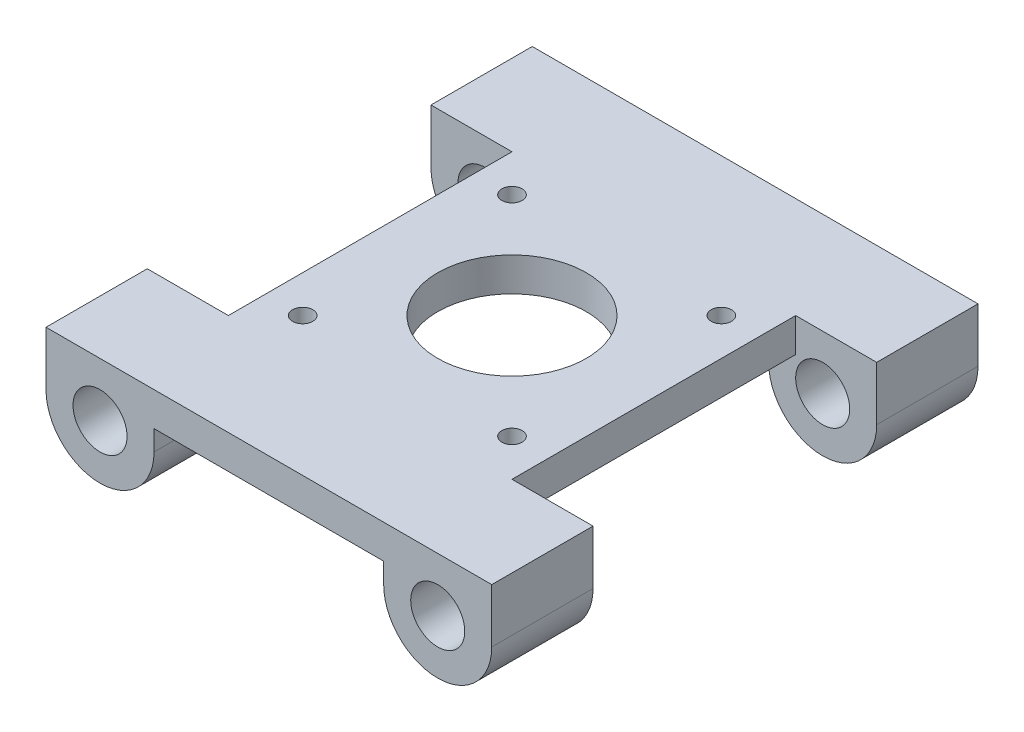
SolidWorks part; units mm, degrees
material "ABS"
ref_plane "Front Plane" through (0, 0, 0) normal (0, 0, 1) x (1, 0, 0)
ref_plane "Top Plane" through (0, 0, 0) normal (0, 1, 0) x (1, 0, 0)
ref_plane "Right Plane" through (0, 0, 0) normal (1, 0, 0) x (0, 0, -1)
sketch "Sketch1" plane through (0, 0, 0) normal (0, 0, 1) x (1, 0, 0)
  line L0 (0, 74.8863) -> (0, -94.3789) construction
  line L1 (33, 0) -> (-33, 0)
  line L2 (-33, 0) -> (-33, -8)
  line L3 (17, -5) -> (-17, -5)
  line L4 (-17, -5) -> (-17, -8)
  line L5 (17, -5) -> (17, -8)
  line L6 (33, 0) -> (33, -8)
  circle A0 centre (-25, -8) radius 4
  arc A1 (-33, -8) -> (-17, -8) centre (-25, -8) ccw
  arc A2 (33, -8) -> (17, -8) centre (25, -8) cw
  circle A3 centre (25, -8) radius 4
  point P16 (0, -5)
  point P17 (0, 0)
  dimension "D1" = 8
  dimension "D5" = 8
  dimension "D2" = 25
  dimension "D3" = 8
  dimension "D4" = 5
extrude "Boss-Extrude1" add sketch "Sketch1" against normal blind 15
sketch "Sketch2" plane through (0, 0, -15) normal (0, 0, -1) x (-1, 0, 0)
  line L0 (21, 0) -> (-21, 0)
  line L1 (-33, 0) -> (33, 0) construction
  line L2 (-21, 0) -> (-21, -5)
  line L3 (-21, -5) -> (21, -5)
  line L4 (17, -5) -> (-17, -5) construction
  line L5 (0, 7.9638) -> (0, -15.9981) construction
  line L6 (21, 0) -> (21, -5)
  point P12 (0, -5)
  point P13 (0, 0)
  dimension "D1" = 21
extrude "Boss-Extrude2" add sketch "Sketch2" along normal blind 42
extrude "Boss-Extrude3" add sketch "Sketch1<2>" against normal blind 15 from vertex starting at point (-21, 0, -57)
sketch "Sketch1<2>" plane through (0, 0, 0) normal (0, 0, 1) x (1, 0, 0) same geometry as "Sketch1"
sketch "Sketch3" plane through (0, 0, 0) normal (0, 1, 0) x (1, 0, 0)
  line L0 (0, -9.6218) -> (0, 80.5515) construction
  line L1 (-21, 36) -> (21, 36) construction
  line L2 (-21, 57) -> (-21, 15) construction
  line L3 (21, 57) -> (21, 15) construction
  circle A0 centre (-15.5, 51.5) radius 1.5
  circle A1 centre (0, 36) radius 11
  circle A2 centre (15.5, 51.5) radius 1.5
  circle A3 centre (15.5, 20.5) radius 1.5
  circle A4 centre (-15.5, 20.5) radius 1.5
  dimension "D1" = 3
  dimension "D4" = 22
  dimension "D2" = 15.5
  dimension "D3" = 15.5
  dimension "D5" = 2
  dimension "D6" = 2
extrude "Cut-Extrude1" cut sketch "Sketch3" against normal through all
equation "\"rod_diameter\"= 8"
equation "\"rod_hole_thickness\"= 4"
equation "\"rod_radius\"= \"rod_diameter\" / 2"
equation "\"platter_diameter\"= 320"
equation "\"platter_radius\"= \"platter_diameter\" / 2"
equation "\"extruder_mount_hole_spacing\"= 75"
equation "\"arm_rod_spacing\"= 40"
equation "\"top_frame_rod_spacing\"= \"arm_rod_spacing\" + 40"
equation "\"motor_level_rod_spacing\"= 15"
equation "\"linear_bearing_diameter\"= 15"
equation "\"z_rod_spacing\"= 75"
equation "\"platter_rod_spacing\"= 50"
equation "\"rod_nut_thickness\"= 6.5"
equation "\"rod_nut_inscribed_diameter\"= 13"
equation "\"z_height\"= 350"
equation "\"D1@Sketch1\"=\"rod_diameter\""
equation "\"D2@Sketch1\"=\"platter_rod_spacing\"/2"
equation "\"D3@Sketch1\"=\"rod_radius\"+\"rod_hole_thickness\""
equation "\"D5@Sketch1\"=\"rod_radius\"+\"rod_hole_thickness\""
equation "\"D2@Sketch3\"=31/2"
